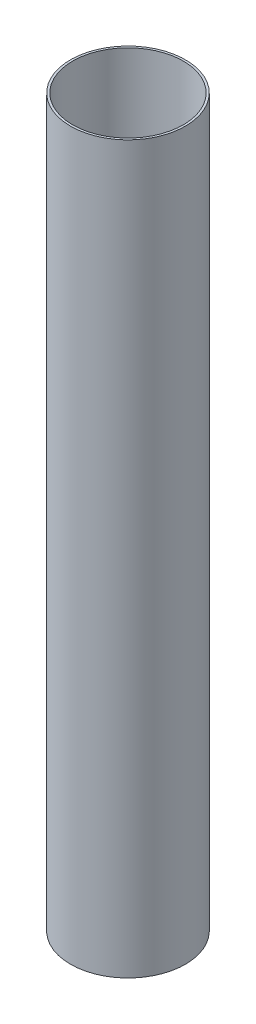
SolidWorks part; units mm, degrees
ref_plane "Front Plane" through (0, 0, 0) normal (0, 0, 1) x (1, 0, 0)
ref_plane "Top Plane" through (0, 0, 0) normal (0, 1, 0) x (1, 0, 0)
ref_plane "Right Plane" through (0, 0, 0) normal (1, 0, 0) x (0, 0, -1)
sketch "Sketch1" plane through (0, 0, 0) normal (0, 1, 0) x (1, 0, 0)
  circle A0 centre (0, 0) radius 38.1
  circle A1 centre (0, 0) radius 39.6
  dimension "D1" = 76.2
  dimension "D2" = 1.5
extrude "Boss-Extrude1" add sketch "Sketch1" along normal blind 500
sketch "Sketch2" plane through (0, 0, 0) normal (1, 0, 0) x (0, 0, -1)
  line L0 (39.6, 500) -> (-39.6, 500) construction
  circle A0 centre (0, 289) radius 2
  dimension "D1" = 4
  dimension "D2" = 211
extrude "Cut-Extrude1" cut sketch "Sketch2" against normal up to surface (39.5495 mm away) up to face at (0, 500, 39.6)
